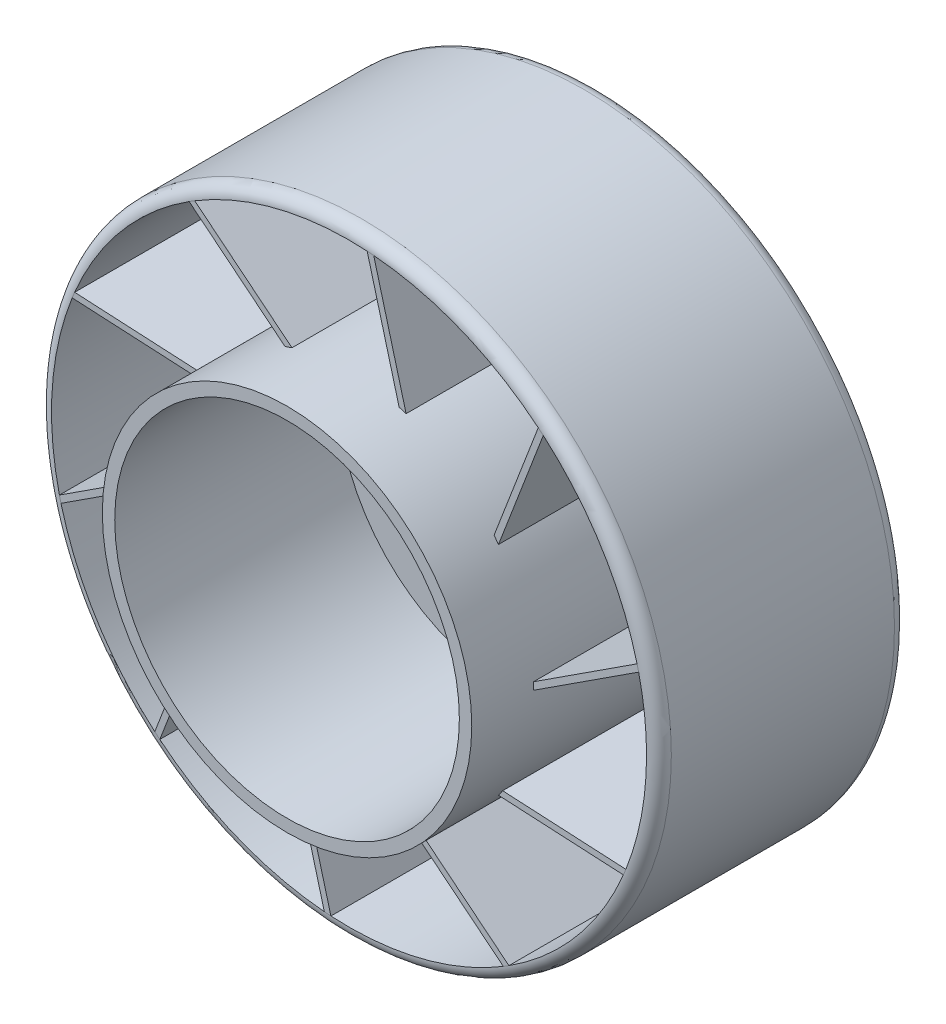
SolidWorks part; units mm, degrees
ref_plane "Front Plane" through (0, 0, 0) normal (0, 0, 1) x (1, 0, 0)
ref_plane "Top Plane" through (0, 0, 0) normal (0, 1, 0) x (1, 0, 0)
ref_plane "Right Plane" through (0, 0, 0) normal (1, 0, 0) x (0, 0, -1)
sketch "Sketch1" plane through (0, 0, 0) normal (0, 0, 1) x (1, 0, 0)
  line L0 (-33.9097, 0) -> (38.3352, 0) construction
  line L1 (0, 26.8691) -> (0, -27.214) construction
  line L2 (14.9, 0) -> (23.362, 5.4972)
  line L3 (14.8884, 0.5887) -> (23.2351, 6.011)
  line L4 (12.391, -8.2749) -> (22.3307, -8.7943)
  line L5 (12.0544, -8.758) -> (22.1314, -9.2845)
  line L6 (5.1606, -13.9778) -> (12.8968, -20.2404)
  line L7 (4.6044, -14.1707) -> (12.4474, -20.5198)
  line L8 (-4.0409, -14.3416) -> (-1.4633, -23.9554)
  line L9 (-4.6044, -14.1707) -> (-1.9911, -23.9173)
  line L10 (-11.6989, -9.2274) -> (-15.2644, -18.5202)
  line L11 (-12.0544, -8.758) -> (-15.6691, -18.1791)
  line L12 (-14.8884, -0.5887) -> (-23.2351, -6.011)
  line L13 (-14.9, 0) -> (-23.362, -5.4972)
  line L14 (-12.391, 8.2749) -> (-22.3307, 8.7943)
  line L15 (-12.0544, 8.758) -> (-22.1314, 9.2845)
  line L16 (-5.1606, 13.9778) -> (-12.8968, 20.2404)
  line L17 (-4.6044, 14.1707) -> (-12.4474, 20.5198)
  line L18 (4.0409, 14.3416) -> (1.4633, 23.9554)
  line L19 (4.6044, 14.1707) -> (1.9911, 23.9173)
  line L20 (11.6989, 9.2274) -> (15.2644, 18.5202)
  line L21 (12.0544, 8.758) -> (15.6691, 18.1791)
  circle A0 centre (0, 0) radius 13.9
  arc A1 (14.8884, 0.5887) -> (12.0544, 8.758) centre (0, 0) ccw
  circle A2 centre (0, 0) radius 25
  arc A3 (23.2351, 6.011) -> (15.6691, 18.1791) centre (0, 0) ccw
  circle A4 centre (0, 0) radius 24 construction
  arc A5 (11.6989, 9.2274) -> (4.6044, 14.1707) centre (0, 0) ccw
  arc A6 (15.2644, 18.5202) -> (1.9911, 23.9173) centre (0, 0) ccw
  arc A7 (1.4633, 23.9554) -> (-12.4474, 20.5198) centre (0, 0) ccw
  arc A8 (4.0409, 14.3416) -> (-4.6044, 14.1707) centre (0, 0) ccw
  arc A9 (-5.1606, 13.9778) -> (-12.0544, 8.758) centre (0, 0) ccw
  arc A10 (-12.8968, 20.2404) -> (-22.1314, 9.2845) centre (0, 0) ccw
  arc A11 (-22.3307, 8.7943) -> (-23.362, -5.4972) centre (0, 0) ccw
  arc A12 (-12.391, 8.2749) -> (-14.9, 0) centre (0, 0) ccw
  arc A13 (-14.8884, -0.5887) -> (-12.0544, -8.758) centre (0, 0) ccw
  arc A14 (-23.2351, -6.011) -> (-15.6691, -18.1791) centre (0, 0) ccw
  arc A15 (-11.6989, -9.2274) -> (-4.6044, -14.1707) centre (0, 0) ccw
  arc A16 (-15.2644, -18.5202) -> (-1.9911, -23.9173) centre (0, 0) ccw
  arc A17 (-4.0409, -14.3416) -> (4.6044, -14.1707) centre (0, 0) ccw
  arc A18 (5.1606, -13.9778) -> (12.0544, -8.758) centre (0, 0) ccw
  arc A19 (12.391, -8.2749) -> (14.9, 0) centre (0, 0) ccw
  arc A20 (12.8968, -20.2404) -> (22.1314, -9.2845) centre (0, 0) ccw
  arc A21 (-1.4633, -23.9554) -> (12.4474, -20.5198) centre (0, 0) ccw
  arc A22 (22.3307, -8.7943) -> (23.362, 5.4972) centre (0, 0) ccw
  dimension "D1" = 27.8
  dimension "D2" = 1
  dimension "D3" = 50
  dimension "D6" = 0.5
  dimension "D4" = 1
  dimension "D5" = 10
extrude "Boss-Extrude1" add sketch "Sketch1" along normal blind 20
fillet "Fillet1" radius 1 2 edges at (25, 0, 0) (25, 0, 20)
sketch "Sketch2" plane through (0, 0, 0) normal (0, 0, -1) x (-1, 0, 0)
  circle A0 centre (0, 0) radius 13.9 construction
  circle A1 centre (0, 0) radius 13.9
extrude "Boss-Extrude2" add sketch "Sketch2" against normal blind 7
sketch "Sketch3" plane through (0, 0, 0) normal (0, 0, -1) x (-1, 0, 0)
  circle A0 centre (0, 0) radius 4.125
  dimension "D1" = 8.25
extrude "Cut-Extrude1" cut sketch "Sketch3" against normal through all
sketch "Sketch4" plane through (0, 0, 7) normal (0, 0, 1) x (1, 0, 0)
  circle A0 centre (0, 0) radius 4.6
  dimension "D1" = 9.2
extrude "Cut-Extrude2" cut sketch "Sketch4" against normal blind 2.3
sketch "Sketch8" plane through (0, 0, 20) normal (0, 0, 1) x (1, 0, 0)
  circle A2 centre (0, 0) radius 13.9 construction
  circle A3 centre (0, 0) radius 14.9
  circle A4 centre (0, 0) radius 14.9
  circle A5 centre (0, 0) radius 13.9
  dimension "D1" = 1
extrude "Boss-Extrude3" add sketch "Sketch8" along normal blind 5
sketch "Sketch9" plane through (0, 0, 0) normal (0, 0, -1) x (-1, 0, 0)
  circle A0 centre (-5.1962, 3) radius 1.15
  circle A1 centre (5.1962, 3) radius 1.15
  circle A2 centre (0, -6) radius 1.15
  dimension "D1" = 2.3
  dimension "D2" = 2.3
  dimension "D3" = 2.3
extrude "Cut-Extrude3" cut sketch "Sketch9" against normal through all
chamfer "Chamfer1" distance 1 angle 45 3 edges at (4.0462, 3, 0) (-1.15, -6, 0) (-6.3462, 3, 0)
